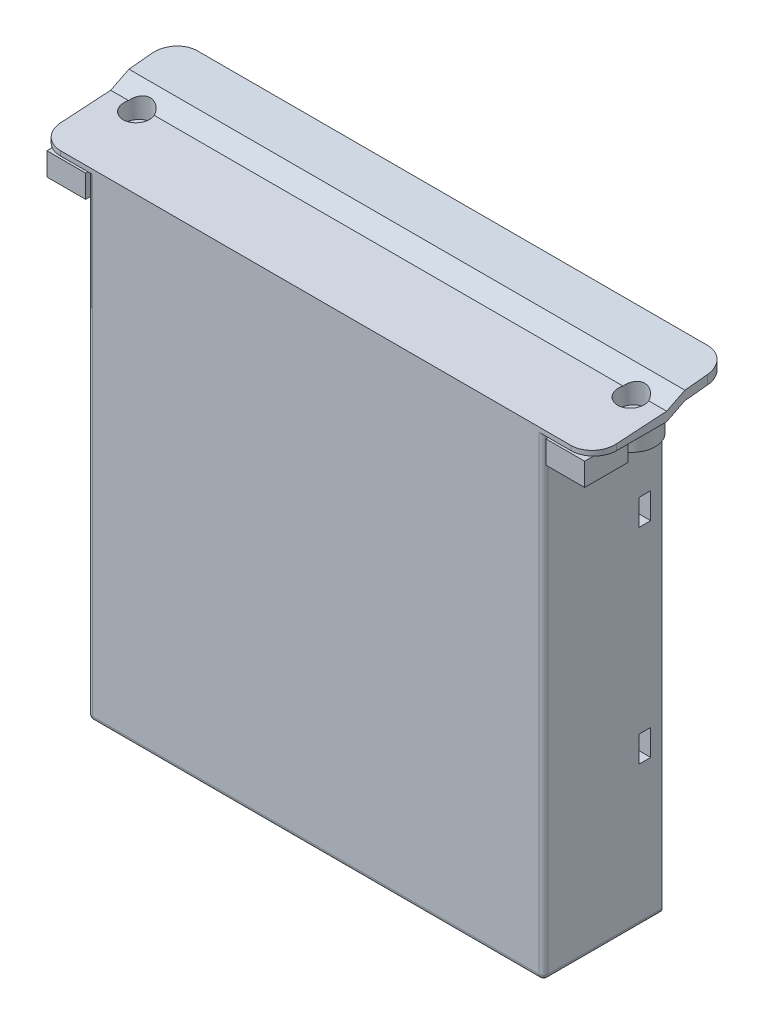
SolidWorks part; units mm, degrees
ref_plane "Front Plane" through (0, 0, 0) normal (0, 0, 1) x (1, 0, 0)
ref_plane "Top Plane" through (0, 0, 0) normal (0, 1, 0) x (1, 0, 0)
ref_plane "Right Plane" through (0, 0, 0) normal (1, 0, 0) x (0, 0, -1)
sketch "Sketch1" plane through (0, 0, 0) normal (0, 1, 0) x (1, 0, 0)
  line L1 (-50, 15) -> (50, 15)
  line L2 (-50, 15) -> (-50, -15)
  line L3 (-50, -15) -> (50, -15)
  line L4 (50, 15) -> (50, -15)
  line L5 (-50, 15) -> (50, -15) construction
  line L6 (-50, -15) -> (50, 15) construction
  point P0 (0, 0)
  dimension "D1" = 100
  dimension "D2" = 30
extrude "Boss-Extrude1" add sketch "Sketch1" against normal blind 99 and the other way blind 6
sketch "Sketch3" plane through (0, 0, 0) normal (1, 0, 0) x (0, 0, -1)
  line L0 (15, 0) -> (15, 10) construction
  line L1 (-15, 0) -> (-15, 6) construction
  line L2 (15, 10) -> (5, 9)
  line L3 (5, 9) -> (5, 10) construction
  line L4 (5, 10) -> (15, 10) construction
  line L5 (5, 9) -> (1, 7)
  line L6 (1, 7) -> (1, 9) construction
  line L7 (1, 9) -> (5, 9) construction
  line L8 (1, 7) -> (-15, 6)
  line L9 (-15, 6) -> (-15, 5)
  line L10 (-15, 5) -> (1, 5)
  line L11 (1, 5) -> (5, 7)
  line L12 (5, 7) -> (15, 8)
  line L13 (15, 8) -> (15, 10)
  line L15 (16.5, 0) -> (-16.5, 0) construction
  dimension "D1" = 10
  dimension "D2" = 6
  dimension "D3" = 10
  dimension "D4" = 1
  dimension "D5" = 4
  dimension "D6" = 2
  dimension "D7" = 1
  dimension "D8" = 2
  dimension "D9" = 2
  dimension "D10" = 2
  dimension "D11" = 4
extrude "Boss-Extrude3" add sketch "Sketch3" along normal blind 61 and the other way blind 61
sketch "Sketch2" plane through (0, 0, 0) normal (0, 1, 0) x (1, 0, 0)
  line L0 (2.0351, 0) -> (-75.861, 0) construction
  line L3 (-49, 10.8492) -> (-49, -4.511) construction
  line L4 (-50, 15) -> (-50, 3) construction
  line L5 (49, 38.0756) -> (49, 0.2251) construction
  line L6 (50, 3) -> (50, 15) construction
  circle A0 centre (-54.25, 0) radius 5.25
  circle A1 centre (54.25, 0) radius 5.25
  circle A2 centre (-54.25, 0) radius 1.35
  circle A3 centre (54.25, 0) radius 1.35
  dimension "D1" = 10.5
  dimension "D3" = 1
  dimension "D4" = 10.5
  dimension "D5" = 2.7
  dimension "D6" = 2.7
  dimension "D2" = 1
extrude "Boss-Extrude2" add sketch "Sketch2" along normal up to surface (1.875 mm away) up to face at (0, 5.75, -2.5)
sketch "Sketch9" plane through (0, 0, 0) normal (0, 1, 0) x (1, 0, 0)
  line L0 (2.0351, 0) -> (-75.861, 0) construction
  line L3 (-49, 10.8492) -> (-49, -4.511) construction
  line L5 (49, 38.0756) -> (49, 0.2251) construction
  circle A0 centre (-54.25, 0) radius 5.25
  circle A1 centre (54.25, 0) radius 5.25
  circle A2 centre (-54.25, 0) radius 1.75
  circle A3 centre (54.25, 0) radius 1.75
  dimension "D1" = 10.5
  dimension "D4" = 10.5
  dimension "D5" = 3.5
  dimension "D6" = 3.5
extrude "Boss-Extrude5" add sketch "Sketch9" along normal up to surface (5 mm away) up to face at (-55.7006, 5, 3.5714)
sketch "Sketch5" plane through (0, 0, 0) normal (0, 1, 0) x (1, 0, 0)
  circle A0 centre (-54.25, 0) radius 1.6
  circle A1 centre (54.25, 0) radius 1.6
  dimension "D2" = 3.2
extrude "Cut-Extrude1" cut sketch "Sketch5" along normal blind 10
sketch "Sketch4" plane through (0, 6, 0) normal (0, 1, 0) x (1, 0, 0)
  line L0 (50, 3.0822) -> (50, 15) construction
  line L1 (-50, 15) -> (50, 15)
  line L2 (-50, 15) -> (-50, 3)
  line L3 (-50, 3) -> (50, 3)
  line L4 (50, 15) -> (50, 3)
  dimension "D1" = 12
extrude "Boss-Extrude4" add sketch "Sketch4" along normal blind 2
sketch "Sketch6" plane through (0, 6.9105, 0.4319) normal (0, 0.9981, 0.0624) x (1, 0, 0)
  circle A0 centre (-54.25, 0.4327) radius 3
  circle A1 centre (54.25, 0.4327) radius 3
  dimension "D1" = 6
  dimension "D2" = 6
extrude "Cut-Extrude2" cut sketch "Sketch6" against normal blind 4 and the other way blind 1
fillet "Fillet5" radius 1 8 edges at (-50, -99, 0) (50, -99, 0) (0, -99, -15) (0, -99, 15) (50, -47, 15) (-50, -47, 15) (-50, -45.5, -15) (50, -45.5, -15)
fillet "Fillet6" radius 5 4 edges at (61, 9, -15) (61, 5.5, 15) (-61, 5.5, 15) (-61, 9, -15)
sketch "Sketch7" plane through (0, -99, 0) normal (0, -1, 0) x (1, 0, 0)
  line L0 (49, -15) -> (-49, -15) construction
  line L1 (-47, 12) -> (47, 12)
  line L2 (-47, -11) -> (-47, 12)
  line L3 (-47, -15) -> (47, -15)
  line L4 (47, -11) -> (47, 12)
  line L5 (-47, 12) -> (47, -15) construction
  line L6 (-47, -15) -> (47, 12) construction
  line L7 (0, 14) -> (0, -4.891) construction
  line L8 (-47, -11) -> (-50, -11)
  line L9 (-50, -14) -> (-50, -5) construction
  line L10 (49, 14) -> (-49, 14) construction
  line L11 (-50, -11) -> (-50, -15)
  line L12 (-56, -15) -> (-49, -15) construction
  line L13 (-50, -15) -> (-47, -15)
  line L14 (47, -11) -> (50, -11)
  line L15 (50, -5) -> (50, -14) construction
  line L16 (50, -11) -> (50, -15)
  line L17 (49, -15) -> (56, -15) construction
  line L18 (50, -15) -> (47, -15)
  point P0 (0, -1.5)
  dimension "D1" = 27
  dimension "D2" = 94
  dimension "D3" = 4
  dimension "D4" = 4
extrude "Cut-Extrude3" cut sketch "Sketch7" against normal blind 99
sketch "Sketch10" plane through (0, 0, 12) normal (0, 0, -1) x (-1, 0, 0)
  text T0 "EDSPack v18.3.10\r\nCase\r\n2019-05-11_1802"
extrude "Cut-Extrude4" cut sketch "Sketch10" against normal blind 1
sketch "Sketch11" plane through (0, 0, 12) normal (0, 0, -1) x (-1, 0, 0)
  line L0 (47, 0) -> (47, -99) construction
  line L1 (-47, -99) -> (47, -99)
  line L2 (-47, -99) -> (-47, -83)
  line L3 (-47, -83) -> (47, -83)
  line L4 (47, -99) -> (47, -83)
  dimension "D1" = 16
extrude "Boss-Extrude6" add sketch "Sketch11" along normal blind 18.5
sketch "Sketch12" plane through (0, 0, 12) normal (0, 0, -1) x (-1, 0, 0)
  line L0 (47, -83) -> (-47, -83) construction
  line L1 (-47, 0) -> (-40.5, 0)
  line L2 (-47, 0) -> (-47, -83)
  line L3 (-47, -83) -> (-40.5, -83)
  line L4 (-40.5, 0) -> (-40.5, -83)
  line L6 (47, 0) -> (40.5, 0)
  line L7 (47, 0) -> (47, -83)
  line L8 (47, -83) -> (40.5, -83)
  line L9 (40.5, 0) -> (40.5, -83)
  dimension "D1" = 6.5
  dimension "D2" = 6.5
extrude "Boss-Extrude7" add sketch "Sketch12" along normal blind 23
sketch "Sketch13" plane through (50, 0, 0) normal (1, 0, 0) x (0, 0, -1)
  line L0 (11, 0) -> (11, -98) construction
  line L1 (8.5, -17.35) -> (5.9, -17.35)
  line L2 (8.5, -17.35) -> (8.5, -23.05)
  line L3 (8.5, -23.05) -> (5.9, -23.05)
  line L4 (5.9, -17.35) -> (5.9, -23.05)
  line L5 (8.5, -17.35) -> (5.9, -23.05) construction
  line L6 (8.5, -23.05) -> (5.9, -17.35) construction
  line L7 (14, 0) -> (11, 0) construction
  point P0 (7.2, -20.2)
  dimension "D1" = 2.5
  dimension "D2" = 2.6
  dimension "D3" = 5.7
  dimension "D4" = 20.2
extrude "Cut-Extrude5" cut sketch "Sketch13" against normal blind 7
sketch "Sketch14" plane through (0, 0, -11) normal (0, 0, -1) x (-1, 0, 0)
  line L0 (-50, 0) -> (-50, -98) construction
  line L2 (-50, 0) -> (-40.5, 0) construction
  circle A0 centre (-46.5, -20.2) radius 1.6
  dimension "D3" = 3.2
  dimension "D1" = 3.5
  dimension "D2" = 20.2
extrude "Cut-Extrude6" cut sketch "Sketch14" against normal blind 2.2
sketch "Sketch15" plane through (0, 0, -5.9) normal (0, 0, -1) x (-1, 0, 0)
  line L0 (-43, -17.35) -> (-50, -17.35) construction
  line L1 (-50, -17.35) -> (-50, -23.05) construction
  circle A0 centre (-46.5, -20.2) radius 1.6
  dimension "D3" = 3.2
  dimension "D1" = 2.85
  dimension "D2" = 3.5
extrude "Cut-Extrude7" cut sketch "Sketch15" against normal blind 5
sketch "Sketch16" plane through (43, 0, 0) normal (1, 0, 0) x (0, 0, -1)
  line L0 (5.9, -17.35) -> (5.9, -23.05) construction
  line L1 (7.7, -18.7) -> (6.7, -18.7)
  line L2 (7.7, -18.7) -> (7.7, -21.7)
  line L3 (7.7, -21.7) -> (6.7, -21.7)
  line L4 (6.7, -18.7) -> (6.7, -21.7)
  line L5 (7.7, -18.7) -> (6.7, -21.7) construction
  line L6 (7.7, -21.7) -> (6.7, -18.7) construction
  line L7 (8.5, -17.35) -> (5.9, -17.35) construction
  point P0 (7.2, -20.2)
  dimension "D1" = 1.3
  dimension "D2" = 2.85
  dimension "D3" = 3
  dimension "D4" = 1
extrude "Cut-Extrude8" cut sketch "Sketch16" against normal up to next
pattern_linear "LPattern2" count 2 spacing 45 along (0, -1, 0) of "Cut-Extrude5", "Cut-Extrude6", "Cut-Extrude7", "Cut-Extrude8"
mirror "Mirror5" about plane through (0, 0, 0) normal (1, 0, 0) of "LPattern2", "Cut-Extrude8", "Cut-Extrude7", "Cut-Extrude6", "Cut-Extrude5"
sketch "Sketch17" plane through (0, 0, -11) normal (0, 0, -1) x (-1, 0, 0)
  line L0 (-48.5, -35.2) -> (-45.5, -35.2)
  line L1 (-50, 0) -> (-40.5, 0) construction
  line L3 (-50, 0) -> (-50, -98) construction
  arc A0 (-48.5, -35.2) -> (-45.5, -35.2) centre (-47, -35.2) ccw
  dimension "D1" = 1.5
  dimension "D2" = 35.2
  dimension "D3" = 3
revolve "Revolve1" add sketch "Sketch17" angle 180 about L0 reverse direction yes
pattern_linear "LPattern3" count 2 spacing 15 along (0, -1, 0) of "Revolve1"
mirror "Mirror6" about plane through (0, 0, 0) normal (1, 0, 0) of "LPattern3", "Revolve1"
sketch "Sketch18" plane through (0, 0, 15) normal (0, 0, 1) x (1, 0, 0)
  line L0 (-59.5, 5) -> (-50, 5) construction
  line L1 (-59, 4.5) -> (-50.5, 4.5)
  line L2 (-59, 4.5) -> (-59, -0.5)
  line L3 (-59, -0.5) -> (-50.5, -0.5)
  line L4 (-50.5, 4.5) -> (-50.5, -0.5)
  line L5 (-50, 0) -> (-50, 5) construction
  line L6 (-59.5, 5) -> (-59.5, 0) construction
  line L8 (-59.5, 0) -> (-50, 0) construction
  line L9 (50, 5) -> (59.5, 5) construction
  line L10 (50.5, 4.5) -> (59, 4.5)
  line L11 (50.5, 4.5) -> (50.5, -0.5)
  line L12 (50.5, -0.5) -> (59, -0.5)
  line L13 (59, 4.5) -> (59, -0.5)
  line L14 (50, 0) -> (59.5, 0) construction
  line L15 (59.5, 0) -> (59.5, 5) construction
  line L16 (50, 5) -> (50, 0) construction
  dimension "D1" = 0.5
  dimension "D2" = 0.5
  dimension "D3" = 0.5
  dimension "D4" = 0.5
  dimension "D5" = 0.5
  dimension "D6" = 0.5
  dimension "D7" = 0.5
  dimension "D8" = 0.5
extrude "Boss-Extrude8" add sketch "Sketch18" against normal blind 9.5 separate body
